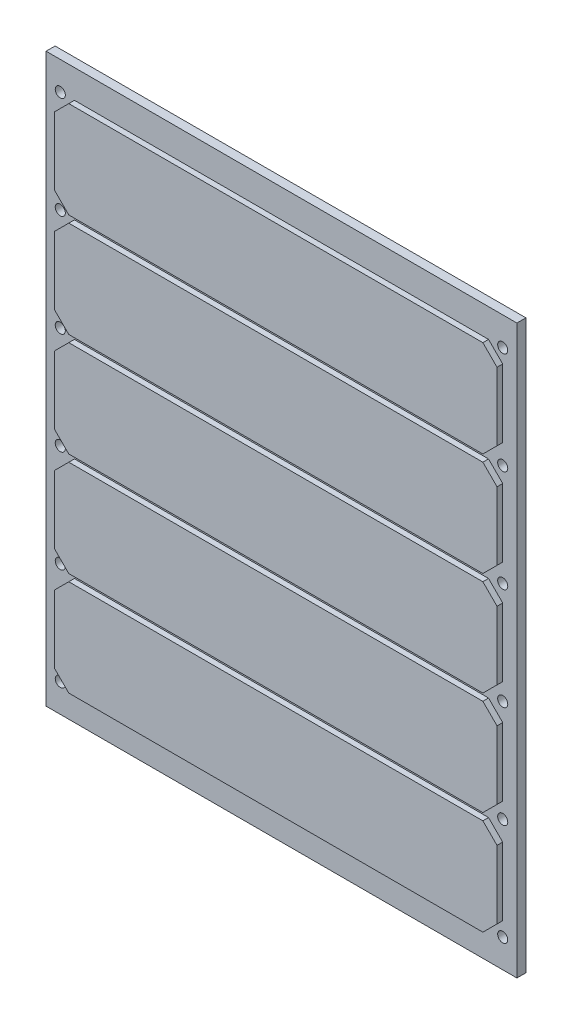
SolidWorks part; units mm, degrees
ref_plane "Front Plane" through (0, 0, 0) normal (0, 0, 1) x (1, 0, 0)
ref_plane "Top Plane" through (0, 0, 0) normal (0, 1, 0) x (1, 0, 0)
ref_plane "Right Plane" through (0, 0, 0) normal (1, 0, 0) x (0, 0, -1)
sketch "Sketch1" plane through (0, 0, 0) normal (0, 0, 1) x (1, 0, 0)
  line L1 (-41.5, -50) -> (41.5, -50)
  line L2 (-41.5, -50) -> (-41.5, 50)
  line L3 (-41.5, 50) -> (41.5, 50)
  line L4 (41.5, -50) -> (41.5, 50)
  line L5 (-41.5, -50) -> (41.5, 50) construction
  line L6 (-41.5, 50) -> (41.5, -50) construction
  point P0 (0, 0)
  dimension "D1" = 83
  dimension "D2" = 100
extrude "Boss-Extrude1" add sketch "Sketch1" along normal blind 1.5875
sketch "Sketch2" plane through (0, 0, 1.5875) normal (0, 0, 1) x (1, 0, 0)
  line L0 (-36.5, 45) -> (36.5, 45)
  line L1 (36.5, 45) -> (39, 42.5)
  line L2 (39, 42.5) -> (39, 30.5)
  line L3 (36.5, 28) -> (-36.5, 28)
  line L4 (-39, 30.5) -> (-39, 42.5)
  line L5 (-39, 42.5) -> (-36.5, 45)
  line L6 (0, 0) -> (0, 50) construction
  line L7 (41.5, 50) -> (-41.5, 50) construction
  line L8 (-36.5, 28) -> (-39, 30.5)
  line L9 (39, 30.5) -> (36.5, 28)
  line L10 (-36.5, 26.75) -> (36.5, 26.75)
  line L11 (36.5, 26.75) -> (39, 24.25)
  line L12 (39, 24.25) -> (39, 12.25)
  line L13 (36.5, 9.75) -> (-36.5, 9.75)
  line L14 (-39, 12.25) -> (-39, 24.25)
  line L15 (-39, 24.25) -> (-36.5, 26.75)
  line L16 (-36.5, 9.75) -> (-39, 12.25)
  line L17 (39, 12.25) -> (36.5, 9.75)
  line L18 (-36.5, 8.5) -> (36.5, 8.5)
  line L19 (36.5, 8.5) -> (39, 6)
  line L20 (39, 6) -> (39, -6)
  line L21 (36.5, -8.5) -> (-36.5, -8.5)
  line L22 (-39, -6) -> (-39, 6)
  line L23 (-39, 6) -> (-36.5, 8.5)
  line L24 (-36.5, -8.5) -> (-39, -6)
  line L25 (39, -6) -> (36.5, -8.5)
  line L26 (-36.5, -9.75) -> (36.5, -9.75)
  line L27 (36.5, -9.75) -> (39, -12.25)
  line L28 (39, -12.25) -> (39, -24.25)
  line L29 (36.5, -26.75) -> (-36.5, -26.75)
  line L30 (-39, -24.25) -> (-39, -12.25)
  line L31 (-39, -12.25) -> (-36.5, -9.75)
  line L32 (-36.5, -26.75) -> (-39, -24.25)
  line L33 (39, -24.25) -> (36.5, -26.75)
  line L34 (-36.5, -28) -> (36.5, -28)
  line L35 (36.5, -28) -> (39, -30.5)
  line L36 (39, -30.5) -> (39, -42.5)
  line L37 (36.5, -45) -> (-36.5, -45)
  line L38 (-39, -42.5) -> (-39, -30.5)
  line L39 (-39, -30.5) -> (-36.5, -28)
  line L40 (-36.5, -45) -> (-39, -42.5)
  line L41 (39, -42.5) -> (36.5, -45)
  line L42 (-41.5, -50) -> (41.5, -50) construction
  point P4 (39, 28)
  point P5 (-39, 28)
  point P20 (39, 9.75)
  point P21 (-39, 9.75)
  point P30 (39, -8.5)
  point P31 (-39, -8.5)
  point P40 (39, -26.75)
  point P41 (-39, -26.75)
  point P50 (39, -45)
  point P51 (-39, -45)
  dimension "D1" = 78
  dimension "D2" = 2.5
  dimension "D3" = 45
  dimension "D4" = 17
  dimension "D5" = 5
  dimension "D7" = 5
  dimension "D6" = 5
extrude "Boss-Extrude2" add sketch "Sketch2" along normal blind 1
hole_wizard "#0 Clearance Hole1" positions "Sketch4" profile "Sketch3" hole size "#0" standard "ANSI Inch"
sketch "Sketch4" plane through (0, 0, 1.5875) normal (0, 0, 1) x (1, 0, 0)
  line L0 (-41.5, 50) -> (-41.5, -50) construction
  line L1 (41.5, 50) -> (-41.5, 50) construction
  line L2 (-41.5, -50) -> (41.5, -50) construction
  line L3 (0, 50) -> (0, -50) construction
  point P56 (-39, 45)
  point P79 (-39, 27)
  point P80 (-39, 9)
  point P81 (-39, -9)
  point P82 (-39, -27)
  point P83 (-39, -45)
  point P91 (39, -45)
  point P92 (39, -27)
  point P93 (39, -9)
  point P94 (39, 9)
  point P95 (39, 27)
  point P96 (39, 45)
  dimension "D1" = 2.5
  dimension "D2" = 5
  dimension "D3" = 6
  dimension "D4" = 5
sketch "Sketch3" plane through (-39, 45, 1.5875) normal (1, 0, 0) x (0, -1, 0)
  line L0 (0, 0) -> (0, 3.7092)
  line L1 (0, 3.7092) -> (0.889, 3.175)
  line L2 (0.889, 3.175) -> (0.889, 0)
  line L5 (0.889, 0) -> (0, 0)
  line L10 (0, 3.7092) -> (-0.889, 3.175) construction
  line L11 (0, -6.35) -> (0, 107.95) construction
  dimension "Hole Dia." = 1.778
  dimension "Hole Depth" = 3.175
  dimension "Drill Angle" = 118
